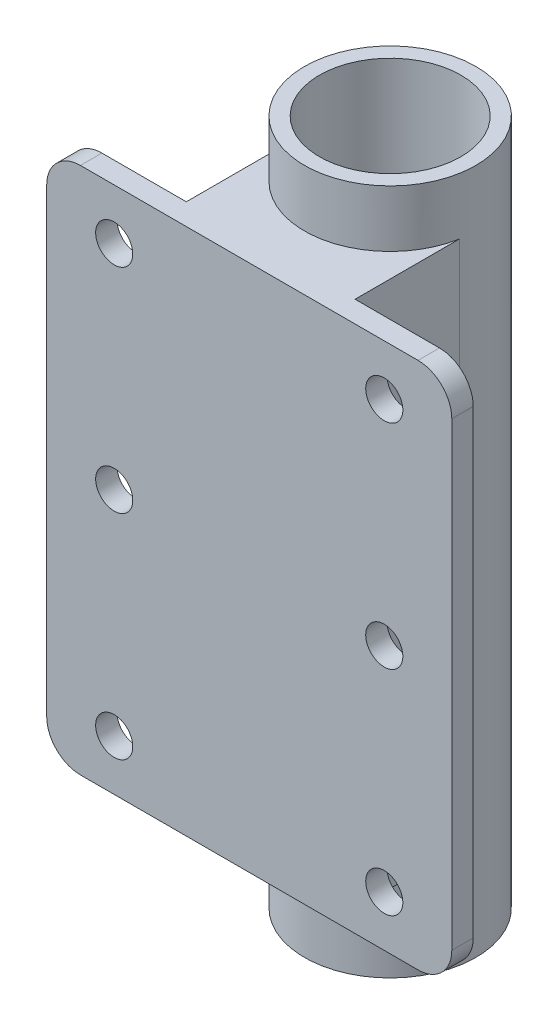
SolidWorks part; units mm, degrees
note: The reader was unsure of these and kept them because the rebuilt part matched: shared geometry of "Sketch14<4>".
other "shoe_support"
other "DetailItem2"
other "DetailItem3"
material "6061 Alloy"
ref_plane "Front Plane" through (0, 0, 0) normal (0, 0, 1) x (1, 0, 0)
ref_plane "Top Plane" through (0, 0, 0) normal (0, 1, 0) x (1, 0, 0)
ref_plane "Right Plane" through (0, 0, 0) normal (1, 0, 0) x (0, 0, -1)
sketch "Sketch11" plane through (0, 0, 0) normal (0, 0, 1) x (1, 0, 0)
  line L0 (0, 0) -> (0, 109.6398) construction
  line L1 (0, 0) -> (-89.1372, 0) construction
sketch "Sketch12" plane through (0, 0, 0) normal (0, 0, 1) x (1, 0, 0)
  line L0 (-25.4, 0) -> (-25.4, 203.2)
  line L1 (200000, 0) -> (-200089.1372, 0) construction
  line L4 (-20.955, 0) -> (-25.4, 0)
  line L5 (-20.955, 0) -> (-20.955, 38.1)
  line L6 (-20.955, 38.1) -> (-19.177, 38.1)
  line L7 (-19.177, 38.1) -> (-19.177, 165.1)
  line L8 (-19.177, 165.1) -> (-20.955, 165.1)
  line L9 (-20.955, 165.1) -> (-20.955, 203.2)
  line L10 (-20.955, 203.2) -> (-25.4, 203.2)
  line L12 (0, -200000) -> (0, 200109.6398) construction
  line L13 (-20.955, 203.2) -> (-15.875, 203.2) construction
  line L14 (-15.875, 203.2) -> (-15.875, 0) construction
  line L15 (-15.875, 0) -> (-20.955, 0) construction
  dimension "D1" = 25.4
  dimension "D2" = 20.955
  dimension "D3" = 19.177
  dimension "D4" = 38.1
  dimension "D5" = 203.2
  dimension "D6" = 4.445
  dimension "D7" = 15.875
revolve "Revolve1" add sketch "Sketch12" angle 360 about L0
ref_plane "mideplane" through (0, 101.6, 0) normal (0, -1, 0) x (-1, 0, 0)
ref_plane "top pipe plane" through (0, 30, 0) normal (0, -1, 0) x (-1, 0, 0)
ref_plane "bottom pipe plane" through (0, 183.2, 0) normal (0, 1, 0) x (1, 0, 0)
ref_plane "pipe support midplane" through (0, 106.6, 0) normal (0, -1, 0) x (-1, 0, 0)
sketch "Sketch14" plane through (0, 30, 0) normal (0, -1, 0) x (-1, 0, 0)
  line L0 (0, 0) -> (-25.4, 0) construction
  line L1 (0, 0) -> (25.4, 0) construction
  line L7 (-25, -35.4) -> (25, -35.4)
  line L9 (25, -35.4) -> (25, -4.49)
  line L10 (-25, -35.4) -> (-25, -4.49)
  line L11 (-21.825, -35.4) -> (-21.825, -12.9934)
  line L12 (21.825, -35.4) -> (21.825, -12.9934)
  circle A0 centre (0, 0) radius 25.4 construction
  circle A1 centre (0, 0) radius 25.4
  circle A2 centre (0, 0) radius 25.4 construction
  arc A3 (25.4, 0) -> (-25.4, 0) centre (0, 0) cw
  dimension "D1" = 0
  dimension "D2" = 10
  dimension "D3" = 50
  dimension "D4" = 3.175
  dimension "D5" = 3.175
extrude "Boss-Extrude1" add sketch "Sketch14" against normal blind 3.175 contours A1 L10 L7 L9
extrude "Boss-Extrude9" add sketch "Sketch14<4>" against normal up to surface (153.2 mm away) contours A1 L10 L7 L11 | A1 L12 L7 L9 up to plane "bottom pipe plane"
sketch "Sketch14<4>" plane through (0, 30, 0) normal (0, -1, 0) x (-1, 0, 0) same geometry as "Sketch14"
sketch "Sketch17" plane through (0, 183.2, 0) normal (0, 1, 0) x (1, 0, 0)
  line L3 (25, -35.4) -> (25, -4.49)
  line L4 (25, -35.4) -> (25, -4.49)
  line L12 (-25, -35.4) -> (25, -35.4)
  line L15 (-25, -4.49) -> (-25, -35.4)
  line L16 (-25, -4.49) -> (-25, -35.4)
  line L17 (-25, -35.4) -> (25, -35.4)
  arc A1 (-25, -4.49) -> (25, -4.49) centre (0, 0) ccw
  arc A6 (-25, -4.49) -> (25, -4.49) centre (0, 0) ccw
  dimension "D1" = 0
extrude "Boss-Extrude5" add sketch "Sketch17" along normal blind 3.175
ref_plane "Plane1" through (0, 0, 35.4) normal (0, 0, 1) x (1, 0, 0)
sketch "Sketch18" plane through (0, 0, 35.4) normal (0, 0, 1) x (1, 0, 0)
  line L0 (0, 30) -> (0, 186.375) construction
  line L1 (-60, 30) -> (60, 30)
  line L2 (-60, 30) -> (-60, 186.375)
  line L3 (-60, 186.375) -> (60, 186.375)
  line L4 (-25, 30) -> (25, 30)
  line L5 (25, 30) -> (25, 186.375)
  line L6 (25, 186.375) -> (-25, 186.375)
  line L7 (-25, 186.375) -> (-25, 30)
  line L8 (-25, 30) -> (25, 30) construction
  line L9 (25, 30) -> (25, 186.375) construction
  line L10 (25, 186.375) -> (-25, 186.375) construction
  line L11 (-25, 186.375) -> (-25, 30) construction
  line L12 (60, 30) -> (60, 186.375)
  line L13 (0, -200000) -> (0, 200109.6398) construction
  line L15 (-40, 171.375) -> (40, 171.375) construction
  line L16 (-40, 171.375) -> (-40, 45) construction
  line L17 (-40, 45) -> (40, 45) construction
  line L18 (40, 171.375) -> (40, 45) construction
  line L19 (-40, 171.375) -> (40, 45) construction
  line L20 (-40, 45) -> (40, 171.375) construction
  circle A2 centre (-40, 45) radius 5 construction
  circle A3 centre (40, 45) radius 5 construction
  circle A4 centre (40, 171.375) radius 5 construction
  circle A5 centre (-40, 171.375) radius 5 construction
  circle A6 centre (-40, 108.1875) radius 5 construction
  circle A7 centre (40, 108.1875) radius 5 construction
  circle A8 centre (-40, 45) radius 8 construction
  point P8 (0, 108.1875)
  dimension "D2" = 10
  dimension "D3" = 15
  dimension "D4" = 10
  dimension "D5" = 15
  dimension "D8" = 16
  dimension "D6" = 0
  dimension "D7" = 0
  dimension "D1" = 0
extrude "Boss-Extrude10" add sketch "Sketch18" along normal blind 6.35
fillet "Fillet1" radius 10 4 edges at (-60, 186.375, 38.575) (60, 186.375, 38.575) (60, 30, 38.575) (-60, 30, 38.575)
hole_wizard "M10 Clearance Hole2" positions "3DSketch2" profile "Sketch20" hole size "M10" standard "ISO" end condition through all
sketch3d "3DSketch2"
  point P0 (-40, 45, 35.4)
  point P3 (-40, 108.1875, 35.4)
  point P6 (-40, 171.375, 35.4)
  point P9 (40, 171.375, 35.4)
  point P12 (40, 108.1875, 35.4)
  point P15 (40, 45, 35.4)
  point P20 (0, 0, 0)
  point P21 (0, 0, 0)
  point P22 (0, 0, 0)
sketch "Sketch20" plane through (-40, 45, 35.4) normal (1, 0, 0) x (0, 1, 0)
  line L0 (0, 0) -> (0, 6.35)
  line L1 (0, 6.35) -> (5.5, 6.35)
  line L2 (5.5, 6.35) -> (5.5, 0)
  line L5 (5.5, 0) -> (0, 0)
  line L11 (0, -6.35) -> (0, 107.95) construction
  dimension "Thru Hole Dia." = 11
  dimension "Thru Hole Depth" = 6.35
